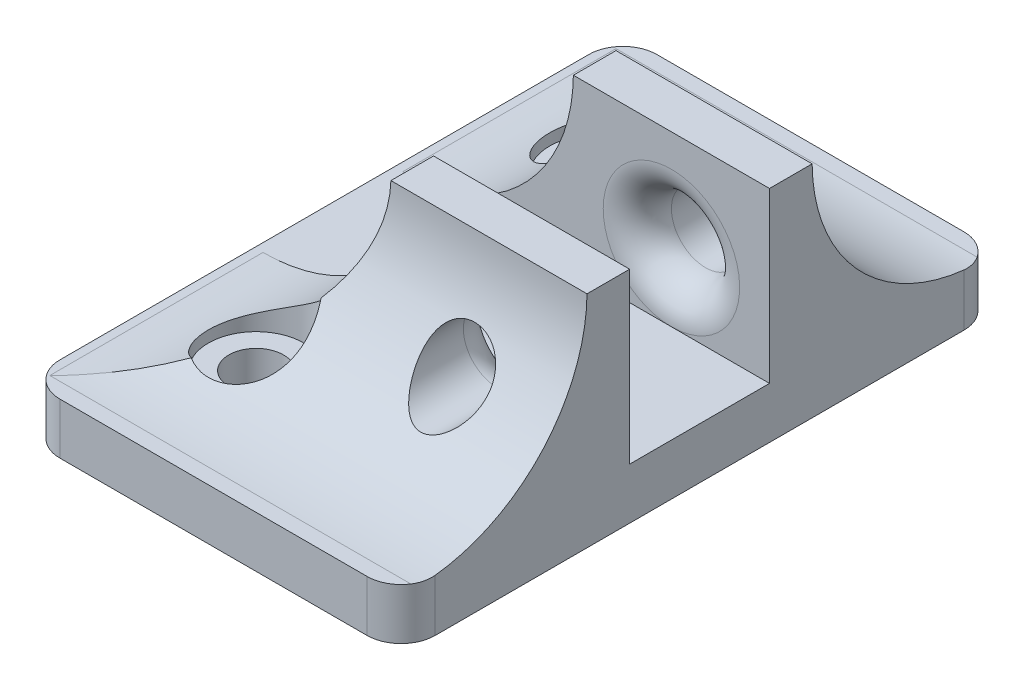
SolidWorks part; units mm, degrees
ref_plane "Alzado" through (0, 0, 0) normal (0, 0, 1) x (1, 0, 0)
ref_plane "Planta" through (0, 0, 0) normal (0, 1, 0) x (1, 0, 0)
ref_plane "Vista lateral" through (0, 0, 0) normal (1, 0, 0) x (0, 0, -1)
sketch "Croquis1" plane through (0, 0, 0) normal (0, 1, 0) x (1, 0, 0)
  line L1 (0, 0) -> (22, 0)
  line L2 (0, 0) -> (0, 35)
  line L3 (0, 35) -> (22, 35)
  line L4 (22, 0) -> (22, 35)
  circle A0 centre (6, 27.5) radius 1.6
  circle A1 centre (6, 7.5) radius 1.6
  dimension "D2" = 3.2
  dimension "D1" = 35
  dimension "D3" = 20
  dimension "D4" = 7.5
  dimension "D5" = 6
  dimension "D6" = 22
extrude "Saliente-Extruir1" add sketch "Croquis1" along normal blind 3
sketch "Croquis2" plane through (0, 3, 0) normal (0, 1, 0) x (1, 0, 0)
  line L0 (22, 0) -> (22, 35) construction
  line L1 (22, 24.1) -> (10.5, 24.1)
  line L2 (22, 24.1) -> (22, 10.9)
  line L3 (22, 10.9) -> (10.5, 10.9)
  line L4 (10.5, 24.1) -> (10.5, 21.6)
  line L5 (10.5, 21.6) -> (22, 21.6)
  line L6 (10.5, 13.4) -> (22, 13.4)
  line L7 (10.5, 13.4) -> (10.5, 10.9)
  line L8 (22, 35) -> (0, 35) construction
  line M9 (22, 0) -> (22, 35)
  dimension "D1" = 13.2
  dimension "D2" = 2.5
  dimension "D3" = 2.5
  dimension "D4" = 10.9
  dimension "D5" = 11.5
extrude "Saliente-Extruir2" add sketch "Croquis2" along normal blind 9.9 contours L4 L5 L2 L1 | L6 L7 L3 M9 region at (16.25, 3, -22.85) region at (16.25, 3, -12.15)
sketch "Croquis4" plane through (0, 0, -21.6) normal (0, 0, 1) x (1, 0, 0)
  line L0 (10.5, 12.9) -> (10.5, 3) construction
  line L1 (10.5, 3) -> (22, 3) construction
  circle A0 centre (16.25, 7) radius 2
  dimension "D1" = 4
  dimension "D2" = 5.75
  dimension "D3" = 4
extrude "Cortar-Extruir1" cut sketch "Croquis4" against normal up to surface (2.5 mm away) up to face at (16.25, 7.95, -24.1)
sketch "Croquis5" plane through (0, 0, -13.4) normal (0, 0, -1) x (-1, 0, 0)
  circle A0 centre (-16.25, 7) radius 2 construction
  circle A1 centre (-16.25, 7) radius 2
extrude "Cortar-Extruir2" cut sketch "Croquis5" against normal up to surface (2.5 mm away) up to face at (16.25, 7.95, -10.9)
sketch "Croquis6" plane through (0, 3, 0) normal (0, 1, 0) x (1, 0, 0)
  circle A0 centre (6, 7.5) radius 2.8
  circle A1 centre (6, 27.5) radius 2.8
  dimension "D1" = 5.6
extrude "Cortar-Extruir3" cut sketch "Croquis6" against normal blind 0.3
fillet "Redondeo1" radius 2 2 edges at (14.25, 7, -13.4) (18.25, 7, -21.6)
fillet "Redondeo2" radius 10 4 edges at (16.25, 3, -24.1) (10.5, 3, -22.85) (10.5, 3, -12.15) (16.25, 3, -10.9)
fillet "Redondeo4" radius 2 4 edges at (0, 1.5, -35) (0, 1.5, 0) (22, 1.5, 0) (22, 1.5, -35)
